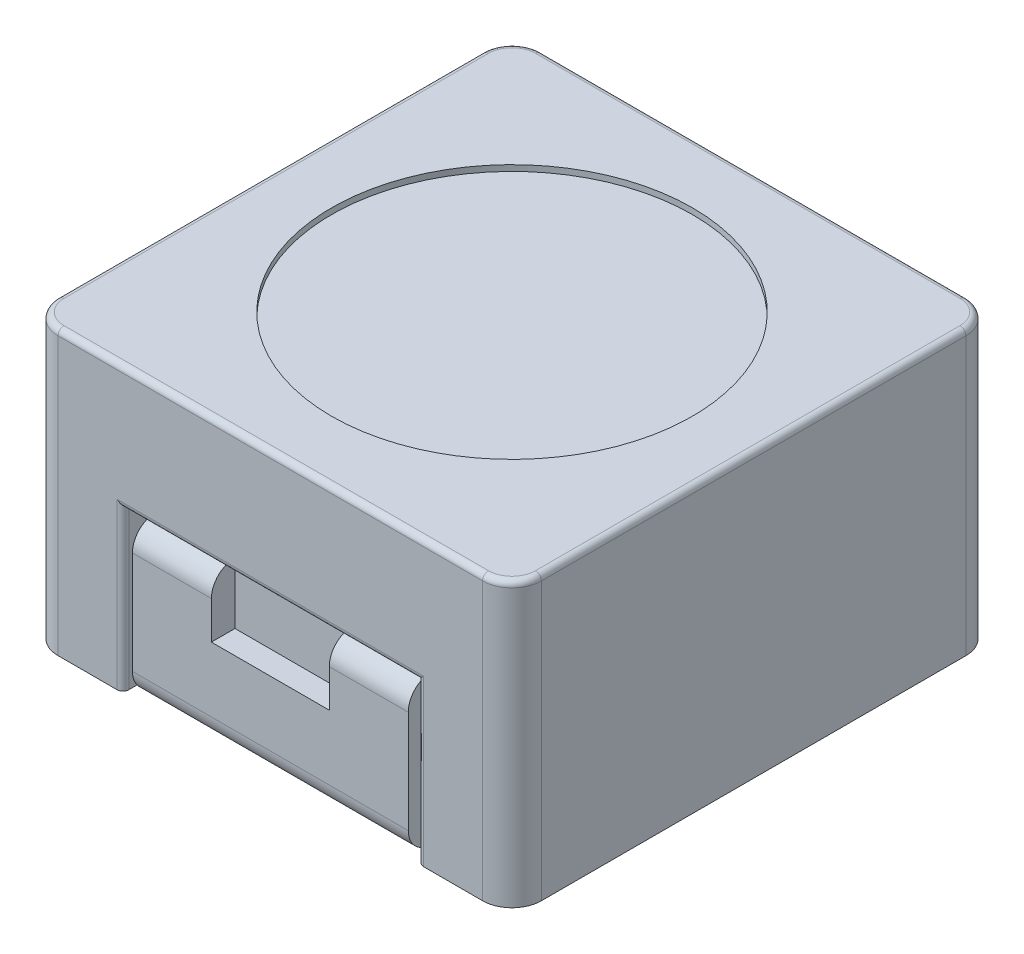
SolidWorks part; units mm, degrees
ref_plane "Спереди" through (0, 0, 0) normal (0, 0, 1) x (1, 0, 0)
ref_plane "Сверху" through (0, 0, 0) normal (0, 1, 0) x (1, 0, 0)
ref_plane "Справа" through (0, 0, 0) normal (1, 0, 0) x (0, 0, -1)
sketch "Эскиз1" plane through (0, 0, 0) normal (0, 1, 0) x (1, 0, 0)
  line L1 (-2.05, -2.05) -> (2.05, -2.05)
  line L2 (-2.05, -2.05) -> (-2.05, 2.05)
  line L3 (-2.05, 2.05) -> (2.05, 2.05)
  line L4 (2.05, -2.05) -> (2.05, 2.05)
  line L5 (-2.05, -2.05) -> (2.05, 2.05) construction
  line L6 (-2.05, 2.05) -> (2.05, -2.05) construction
  point P0 (0, 0)
  dimension "D1" = 4.1
  dimension "D2" = 4.1
extrude "Бобышка-Вытянуть1" add sketch "Эскиз1" along normal blind 2.4
sketch "Эскиз2" plane through (0, 0, 2.05) normal (0, 0, 1) x (1, 0, 0)
  line L0 (-2.05, 0) -> (2.05, 0) construction
  line L1 (-1.25, -1.35) -> (1.25, -1.35)
  line L2 (-1.25, -1.35) -> (-1.25, 1.35)
  line L3 (-1.25, 1.35) -> (1.25, 1.35)
  line L4 (1.25, -1.35) -> (1.25, 1.35)
  line L5 (-1.25, -1.35) -> (1.25, 1.35) construction
  line L6 (-1.25, 1.35) -> (1.25, -1.35) construction
  point P0 (0, 0)
  dimension "D1" = 1.35
  dimension "D2" = 2.5
extrude "Вырез-Вытянуть1" cut sketch "Эскиз2" against normal blind 0.2
sketch "Эскиз3" plane through (0, 0, 1.85) normal (0, 0, 1) x (1, 0, 0)
  line L0 (-1.25, 1.35) -> (-1.25, 0) construction
  line L1 (-1.25, 0.15) -> (1.25, 0.15)
  line L2 (-1.25, 0.15) -> (-1.25, -0.15)
  line L3 (-1.25, -0.15) -> (1.25, -0.15)
  line L4 (1.25, 0.15) -> (1.25, -0.15)
  line L5 (-1.25, 0.15) -> (1.25, -0.15) construction
  line L6 (-1.25, -0.15) -> (1.25, 0.15) construction
  line L7 (1.25, 0) -> (1.25, 1.35) construction
  line L8 (-1.25, 0) -> (1.25, 0) construction
  point P0 (0, 0)
  dimension "D1" = 0.15
extrude "Вырез-Вытянуть2" cut sketch "Эскиз3" against normal blind 1.2
sketch "Эскиз4" plane through (0, 0, -2.05) normal (0, 0, -1) x (-1, 0, 0)
  line L0 (-2.05, 0) -> (2.05, 0) construction
  line L1 (-1.25, -1.35) -> (1.25, -1.35)
  line L2 (-1.25, -1.35) -> (-1.25, 1.35)
  line L3 (-1.25, 1.35) -> (1.25, 1.35)
  line L4 (1.25, -1.35) -> (1.25, 1.35)
  line L5 (-1.25, -1.35) -> (1.25, 1.35) construction
  line L6 (-1.25, 1.35) -> (1.25, -1.35) construction
  point P0 (0, 0)
  dimension "D1" = 2.5
  dimension "D2" = 1.35
extrude "Вырез-Вытянуть3" cut sketch "Эскиз4" against normal blind 0.2
sketch "Эскиз5" plane through (0, 0, -1.85) normal (0, 0, -1) x (-1, 0, 0)
  line L0 (1.25, 0) -> (1.25, 1.35) construction
  line L1 (-1.25, -0.2) -> (1.25, -0.2)
  line L2 (-1.25, -0.2) -> (-1.25, 0.2)
  line L3 (-1.25, 0.2) -> (1.25, 0.2)
  line L4 (1.25, -0.2) -> (1.25, 0.2)
  line L5 (-1.25, -0.2) -> (1.25, 0.2) construction
  line L6 (-1.25, 0.2) -> (1.25, -0.2) construction
  line L8 (-1.25, 1.35) -> (-1.25, 0) construction
  line L10 (-1.25, 0) -> (1.25, 0) construction
  point P0 (0, 0)
  dimension "D1" = 0.2
extrude "Вырез-Вытянуть4" cut sketch "Эскиз5" against normal blind 1.2
sketch "Эскиз6" plane through (0, 2.4, 0) normal (0, 1, 0) x (1, 0, 0)
  circle A0 centre (0, 0) radius 1.5311
extrude "Вырез-Вытянуть6" cut sketch "Эскиз6" against normal blind 0.05
fillet "Скругление3" radius 0.05 10 edges at (1.25, 0.675, -2.05) (-1.25, 0.675, -2.05) (0, 1.35, -2.05) (0, 2.4, -2.05) (2.05, 2.4, 0) (-2.05, 2.4, 0) (0, 2.4, 2.05) (1.25, 0.675, 2.05) (0, 1.35, 2.05) (-1.25, 0.675, 2.05)
fillet "Скругление4" radius 0.25 8 edges at (2.0354, 2.3854, 2.0354) (-2.0354, 2.3854, 2.0354) (-2.0354, 2.3854, -2.0354) (2.0354, 2.3854, -2.0354) (2.05, 1.175, -2.05) (-2.05, 1.175, -2.05) (-2.05, 1.175, 2.05) (2.05, 1.175, 2.05)
sketch "Эскиз8" plane through (0, 0, -1.85) normal (0, 0, -1) x (-1, 0, 0)
  line L0 (-1.17, 0) -> (-1.17, 1.2664)
  line L1 (-1.25, 0) -> (1.25, 0) construction
  line L2 (-1.17, 1.2664) -> (-0.5, 1.2664)
  line L3 (-0.5, 1.2664) -> (-0.5, 0.75)
  line L4 (-0.5, 0.75) -> (0.5, 0.75)
  line L5 (0.5, 0.75) -> (0.5, 1.27)
  line L6 (0.5, 1.27) -> (1.17, 1.27)
  line L7 (1.17, 1.27) -> (1.17, 0.2)
  line L8 (1.25, 0.2) -> (-1.25, 0.2) construction
  line L9 (1.17, 0.2) -> (1.17, 0)
  line L10 (1.17, 0) -> (-1.17, 0)
  line L11 (0, -0.2383) -> (0, 1.7061) construction
  line L12 (-1.25, 1.35) -> (-1.25, 0.2) construction
  line L13 (1.25, 0.2) -> (1.25, 1.35) construction
  line L14 (1.25, 1.35) -> (-1.25, 1.35) construction
  line L15 (-1.25, 1.35) -> (1.25, 1.35) construction
  dimension "D1" = 0.5
  dimension "D2" = 0.5
  dimension "D3" = 0.08
  dimension "D4" = 0.08
  dimension "D5" = 0.0836
  dimension "D6" = 0.08
  dimension "D7" = 0.75
extrude "Бобышка-Вытянуть2" add sketch "Эскиз8" along normal blind 0.2 and the other way blind 1.15 separate body
sketch "Эскиз10" plane through (0, 0, 1.85) normal (0, 0, 1) x (1, 0, 0)
  line L0 (-1.17, 0) -> (-1.17, 1.27)
  line L1 (1.25, 0) -> (-1.25, 0) construction
  line L2 (-1.17, 1.27) -> (-0.5, 1.27)
  line L3 (-0.5, 1.27) -> (-0.5, 0.75)
  line L4 (-0.5, 0.75) -> (0.5, 0.75)
  line L5 (0.5, 0.75) -> (0.5, 1.27)
  line L6 (0.5, 1.27) -> (1.17, 1.27)
  line L7 (1.17, 1.27) -> (1.17, 0.2)
  line L8 (-1.25, 1.35) -> (-1.25, 0.15) construction
  line L9 (1.17, 0.2) -> (1.17, 0)
  line L10 (1.17, 0) -> (-1.17, 0)
  line L11 (0, -0.2383) -> (0, 0.2383) construction
  line L12 (1.25, 0.15) -> (1.25, 1.35) construction
  line L13 (1.25, 1.35) -> (-1.25, 1.35) construction
  dimension "D1" = 0.5
  dimension "D2" = 0.5
  dimension "D3" = 0.08
  dimension "D4" = 0.08
  dimension "D5" = 0.08
  dimension "D6" = 0.08
  dimension "D7" = 0.75
extrude "Бобышка-Вытянуть3" add sketch "Эскиз10" along normal blind 0.2 and the other way blind 1.15
fillet "Скругление7" radius 0.2 3 edges at (0, 0, 2.05) (-0.835, 1.27, 2.05) (0.835, 1.27, 2.05)
fillet "Скругление8" radius 0.2 3 edges at (0, 0, -2.05) (-0.835, 1.27, -2.05) (0.835, 1.2664, -2.05)
